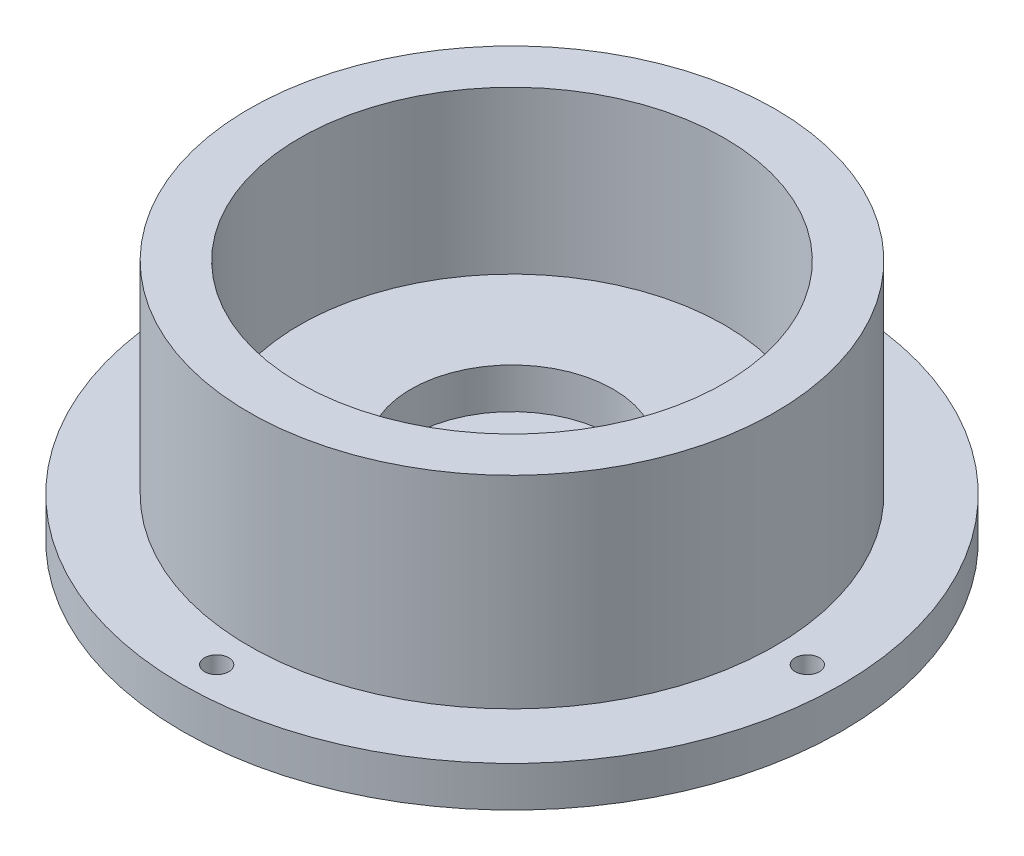
SolidWorks part; units mm, degrees
ref_plane "Front Plane" through (0, 0, 0) normal (0, 0, 1) x (1, 0, 0)
ref_plane "Top Plane" through (0, 0, 0) normal (0, 1, 0) x (1, 0, 0)
ref_plane "Right Plane" through (0, 0, 0) normal (1, 0, 0) x (0, 0, -1)
sketch "Sketch1" plane through (0, 0, 0) normal (1, 0, 0) x (0, 0, -1)
  line L0 (0, 0) -> (25, 0) construction
  line L1 (25, 0) -> (25, -10)
  line L2 (25, 0) -> (52.5, 0)
  line L3 (52.5, 0) -> (52.5, 40)
  line L4 (52.5, 40) -> (65, 40)
  line L5 (65, 40) -> (65, -10)
  line L6 (65, -10) -> (25, -10) construction
  line L7 (0, 0) -> (0, 10) construction
  line L8 (25, -10) -> (0, -10)
  line L9 (0, -10) -> (0, -20)
  line L10 (0, -20) -> (65, -20)
  line L11 (65, -20) -> (65, -10)
  dimension "D1" = 25
  dimension "D2" = 10
  dimension "D3" = 52.5
  dimension "D4" = 40
  dimension "D5" = 10
  dimension "D6" = 40
  dimension "D7" = 10
revolve "Revolve1" add sketch "Sketch1" angle 360 about L7
sketch "Sketch2" plane through (0, 0, 0) normal (0, 1, 0) x (1, 0, 0)
  line L0 (73, 0) -> (0, 0) construction
  line L3 (0, 0) -> (0, 73) construction
  line L6 (-73, 0) -> (0, 0) construction
  line L7 (0, 0) -> (0, -73) construction
  circle A4 centre (0, 73) radius 3
  circle A5 centre (73, 0) radius 3
  circle A6 centre (0, -73) radius 3
  circle A7 centre (-73, 0) radius 3
  circle A8 centre (0, 0) radius 81.5
  dimension "D1" = 6
  dimension "D2" = 163
  dimension "D3" = 73
extrude "Boss-Extrude1" add sketch "Sketch2" along normal blind 10 from surface contours A7 | A4 | A5 | A6 region at (0, 0, 0) starting at face at (0, -20, -65)
